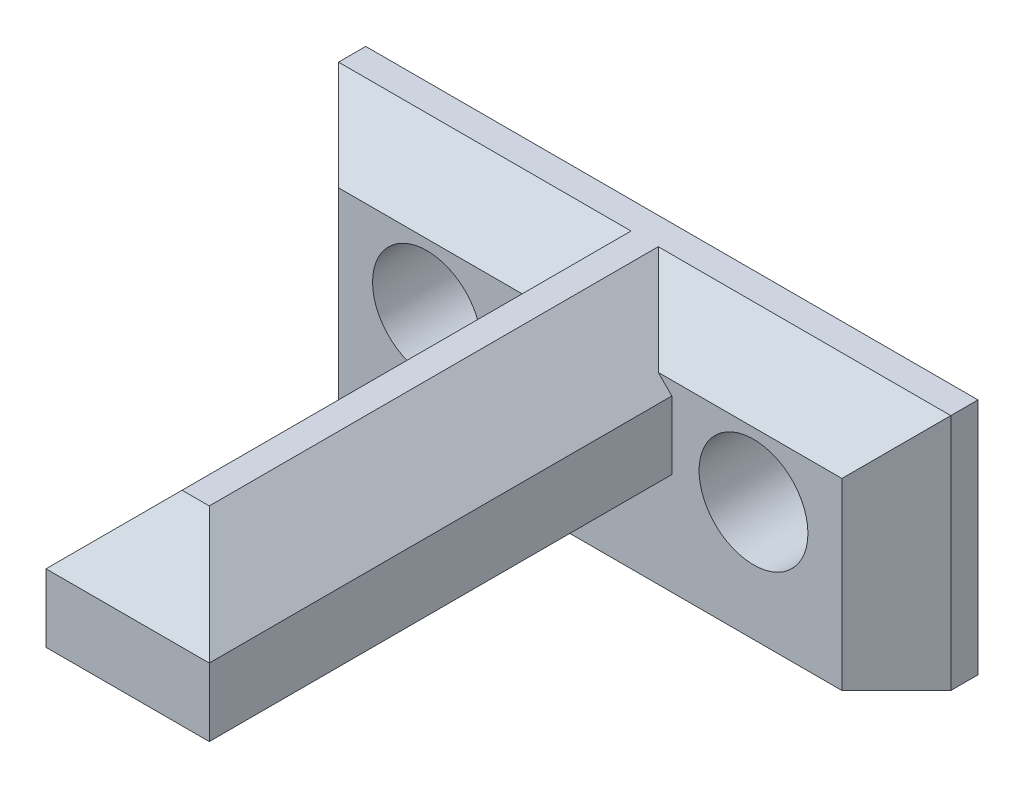
SolidWorks part; units mm, degrees
ref_plane "前视基准面" through (0, 0, 0) normal (0, 0, 1) x (1, 0, 0)
ref_plane "上视基准面" through (0, 0, 0) normal (0, 1, 0) x (1, 0, 0)
ref_plane "右视基准面" through (0, 0, 0) normal (1, 0, 0) x (0, 0, -1)
other "Configuration Table"
sketch "Sketch1" plane through (0, 0, 0) normal (0, 0, 1) x (1, 0, 0)
  line L0 (0, 0) -> (6, 0) construction
  line L1 (-11.25, -4.375) -> (11.25, -4.375)
  line L2 (-11.25, -4.375) -> (-11.25, 4.375)
  line L3 (-11.25, 4.375) -> (11.25, 4.375)
  line L4 (11.25, -4.375) -> (11.25, 4.375)
  line L5 (-11.25, -4.375) -> (11.25, 4.375) construction
  line L6 (-11.25, 4.375) -> (11.25, -4.375) construction
  line L7 (0, 0) -> (0, 4.375) construction
  circle A0 centre (6, 0) radius 2
  circle A1 centre (-6, 0) radius 2
  point P0 (0, 0)
  dimension "D3" = 4
  dimension "D1" = 22.5
  dimension "D2" = 8.75
  dimension "D4" = 6
extrude "Boss-Extrude1" add sketch "Sketch1" along normal blind 3
sketch "Sketch2" plane through (0, 4.375, 0) normal (0, 1, 0) x (1, 0, 0)
  line L0 (-3, 0) -> (3, 0)
  line L1 (11.25, 0) -> (-11.25, 0) construction
  line L6 (3, 0) -> (3, -20)
  line L7 (3, -20) -> (-3, -20)
  line L8 (0, -20) -> (0, 0)
  line L9 (-3, 0) -> (-3, -20)
  line M6 (-11.25, -3) -> (11.25, -3)
  dimension "D1" = 6
  dimension "D2" = 20
extrude "Boss-Extrude2" add sketch "Sketch2" against normal blind 5 contours L9 L7 L8 M6 | L8 L7 L6 M6 region at (-1.5, 4.375, 11.5) region at (1.5, 4.375, 11.5)
chamfer "Chamfer1" distance 2 angle 45 4 edges at (11.25, 0, 3) (7.125, 4.375, 3) (-11.25, 0, 3) (-7.125, 4.375, 3)
chamfer "Chamfer2" distance 2.5 angle 45 3 edges at (3, 4.375, 10.5) (0, 4.375, 20) (-3, 4.375, 10.5)
